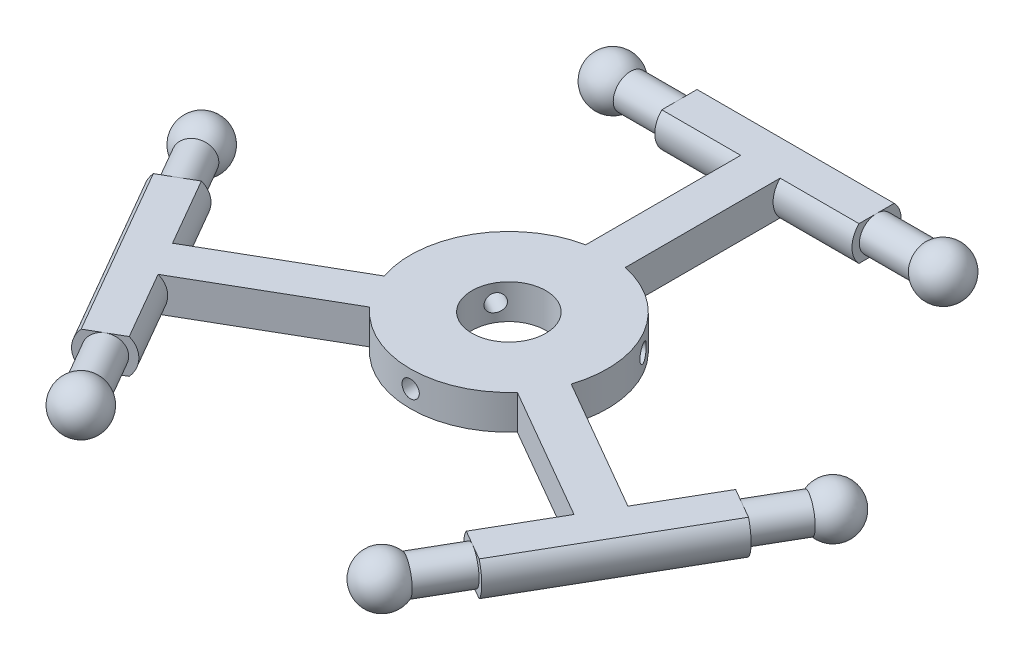
SolidWorks part; units mm, degrees
ref_plane "Front Plane" through (0, 0, 0) normal (0, 0, 1) x (1, 0, 0)
ref_plane "Top Plane" through (0, 0, 0) normal (0, 1, 0) x (1, 0, 0)
ref_plane "Right Plane" through (0, 0, 0) normal (1, 0, 0) x (0, 0, -1)
sketch "Sketch1" plane through (0, 0, 0) normal (0, 1, 0) x (1, 0, 0)
  line L0 (18.9706, -6.3339) -> (49.2815, -23.8339)
  line L2 (-4, 19.5959) -> (-4, 54.5959)
  line L3 (-4, 54.5959) -> (4, 54.5959)
  line L4 (4, 19.5959) -> (4, 54.5959)
  line L6 (14.9706, -13.2621) -> (45.2815, -30.7621)
  line L7 (49.2815, -23.8339) -> (45.2815, -30.7621)
  line L8 (-14.9706, -13.2621) -> (-45.2815, -30.7621)
  line L10 (-18.9706, -6.3339) -> (-49.2815, -23.8339)
  line L11 (-45.2815, -30.7621) -> (-49.2815, -23.8339)
  arc A0 (-4, 19.5959) -> (-18.9706, -6.3339) centre (0, 0) ccw
  circle A1 centre (0, 0) radius 7.5
  arc A2 (-14.9706, -13.2621) -> (14.9706, -13.2621) centre (0, 0) ccw
  arc A3 (18.9706, -6.3339) -> (4, 19.5959) centre (0, 0) ccw
  point P8 (0, 54.5959)
  dimension "D1" = 40
  dimension "D2" = 15
  dimension "D3" = 35
  dimension "D4" = 8
  dimension "D5" = 3
extrude "Boss-Extrude1" add sketch "Sketch1" along normal blind 7
sketch "Sketch2" plane through (0, 0, 0) normal (1, 0, 0) x (0, 0, -1)
  line L0 (54.5959, 7) -> (54.5959, 0) construction
  line L1 (52.9709, 5.7185) -> (56.2209, 5.7185)
  line L2 (51.0252, 7) -> (58.1666, 7)
  line L4 (51.0252, 0) -> (58.1666, 0)
  arc A0 (51.0252, 7) -> (51.0252, 0) centre (54.5959, 3.5) ccw
  arc A1 (52.9709, 5.7185) -> (56.2209, 5.7185) centre (54.5959, 3.5) ccw
  arc A2 (58.1666, 0) -> (58.1666, 7) centre (54.5959, 3.5) ccw
  point P10 (54.5959, 7)
  point P15 (54.5959, 0)
  dimension "D1" = 10
  dimension "D2" = 5.5
  dimension "D3" = 3.25
extrude "Boss-Extrude2" add sketch "Sketch2" along normal mid plane 40
extrude "Cut-Extrude1" cut sketch "Sketch2<2>" against normal mid plane 40 contours L1 A1 region at (0, 3.3733, -54.5959)
sketch "Sketch2<2>" plane through (0, 0, 0) normal (1, 0, 0) x (0, 0, -1) same geometry as "Sketch2"
pattern_circular "CirPattern1" count 3 over 360 about axis through (0, 7, 0) along (0, 1, 0) of "Cut-Extrude1", "Boss-Extrude2"
ref_plane "Plane1" through (17.3205, 0, -10) normal (0.866, 0, -0.5) x (0, -1, 0)
sketch "Sketch3" plane through (17.3205, 0, -10) normal (0.866, 0, -0.5) x (0, -1, 0)
  circle A0 centre (-3.5, 0) radius 1.75
  dimension "D1" = 3.5
  dimension "D2" = 3.5
extrude "Cut-Extrude2" cut sketch "Sketch3" against normal up to next
pattern_circular "CirPattern2" count 3 over 360 about axis through (0, 7, 0) along (0, 1, 0) of "Cut-Extrude2"
sketch "Sketch4" plane through (20, 0, 0) normal (1, 0, 0) x (0, 0, -1)
  circle A0 centre (54.5959, 3.5) radius 3.5
  arc A1 (52.9709, 5.7185) -> (56.2209, 5.7185) centre (54.5959, 3.5) ccw construction
  dimension "D1" = 7
extrude "Boss-Extrude3" add sketch "Sketch4" along normal blind 13.5
sketch "Sketch5" plane through (-20, 0, 0) normal (-1, 0, 0) x (0, 0, 1)
  circle A0 centre (-54.5959, 3.5) radius 3.5
  arc A1 (-56.2209, 5.7185) -> (-52.9709, 5.7185) centre (-54.5959, 3.5) ccw construction
  dimension "D1" = 7
extrude "Boss-Extrude4" add sketch "Sketch5" along normal blind 13.5
pattern_circular "CirPattern3" count 3 every 120 about axis through (0, 7, 0) along (0, -1, 0) of "Boss-Extrude3", "Boss-Extrude4" reverse direction yes
sketch "Sketch6" plane through (-33.5, 0, 0) normal (-1, 0, 0) x (0, 0, 1)
  line L0 (-54.5959, 8.5) -> (-54.5959, -1.5)
  arc A0 (-54.5959, 8.5) -> (-54.5959, -1.5) centre (-54.5959, 3.5) ccw
  circle A1 centre (-54.5959, 3.5) radius 3.5 construction
  dimension "D1" = 5
revolve "Revolve1" add sketch "Sketch6" angle 360 about L0
sketch "Sketch7" plane through (33.5, 0, 0) normal (1, 0, 0) x (0, 0, -1)
  line L0 (54.5959, 8.5) -> (54.5959, -1.5)
  arc A0 (54.5959, 8.5) -> (54.5959, -1.5) centre (54.5959, 3.5) cw
  arc A1 (54.5959, 7) -> (54.5959, 0) centre (54.5959, 3.5) ccw construction
  dimension "D1" = 5
revolve "Revolve2" add sketch "Sketch7" angle 360 about L0
pattern_circular "CirPattern4" count 3 every 120 about axis through (0, 7, 0) along (0, -1, 0) of "Revolve2", "Revolve1"
